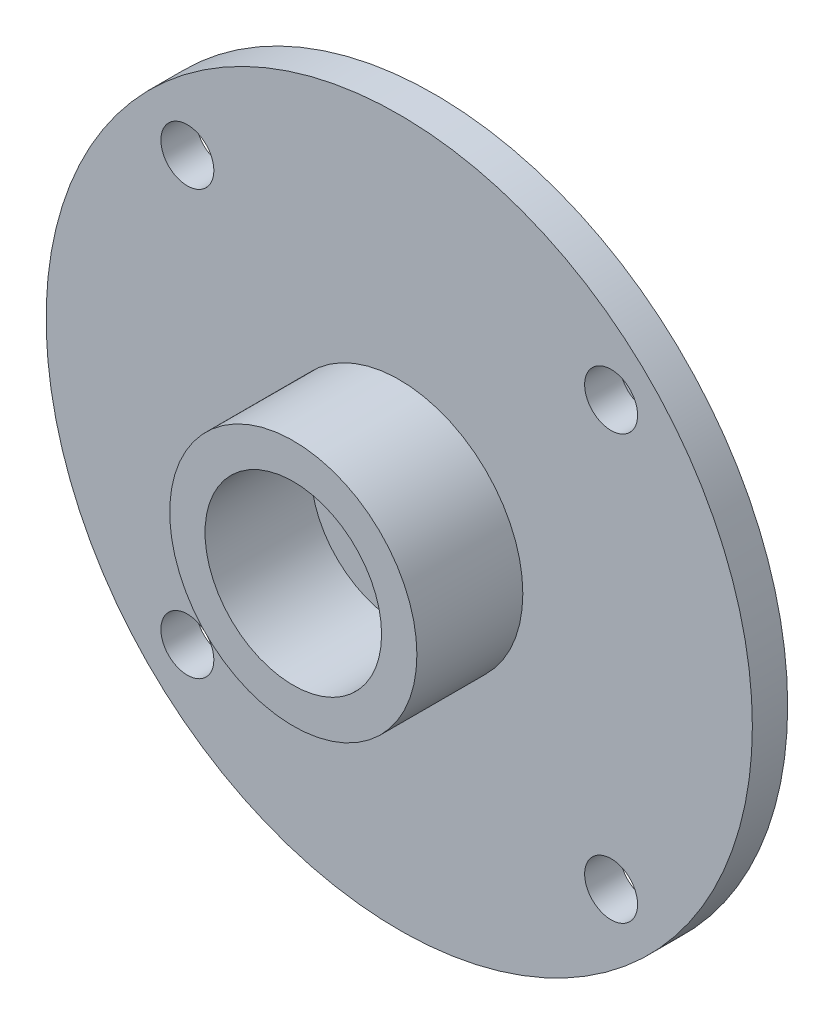
SolidWorks part; units mm, degrees
ref_plane "前视基准面" through (0, 0, 0) normal (0, 0, 1) x (1, 0, 0)
ref_plane "上视基准面" through (0, 0, 0) normal (0, 1, 0) x (1, 0, 0)
ref_plane "右视基准面" through (0, 0, 0) normal (1, 0, 0) x (0, 0, -1)
other "Configuration Table"
sketch "草图1" plane through (0, 0, 0) normal (0, 0, 1) x (1, 0, 0)
  line L5 (-15, 15) -> (15, -15) construction
  line L6 (-15, -15) -> (15, 15) construction
  circle A0 centre (-12, 12) radius 1.5
  circle A1 centre (12, 12) radius 1.5
  circle A2 centre (12, -12) radius 1.5
  circle A3 centre (-12, -12) radius 1.5
  circle A4 centre (0, 0) radius 3
  circle A5 centre (0, 0) radius 20
  point P0 (0, 0)
  point P17 (0, 0)
  dimension "D4" = 4
extrude "凸台-拉伸1" add sketch "草图1" along normal blind 2
sketch "草图2" plane through (0, 0, 2) normal (0, 0, 1) x (1, 0, 0)
  circle A0 centre (0, 0) radius 7
  circle A1 centre (0, 0) radius 5
  dimension "D1" = 14
  dimension "D2" = 10
sketch "草图3" plane through (0, 0, 0) normal (0, 0, -1) x (-1, 0, 0)
  circle A0 centre (0, 0) radius 11
  circle A1 centre (0, 0) radius 7.5
  dimension "D1" = 22
  dimension "D2" = 15
extrude "凸台-拉伸2" add sketch "草图3" along normal blind 5
extrude "凸台-拉伸3" add sketch "草图2" along normal blind 6
